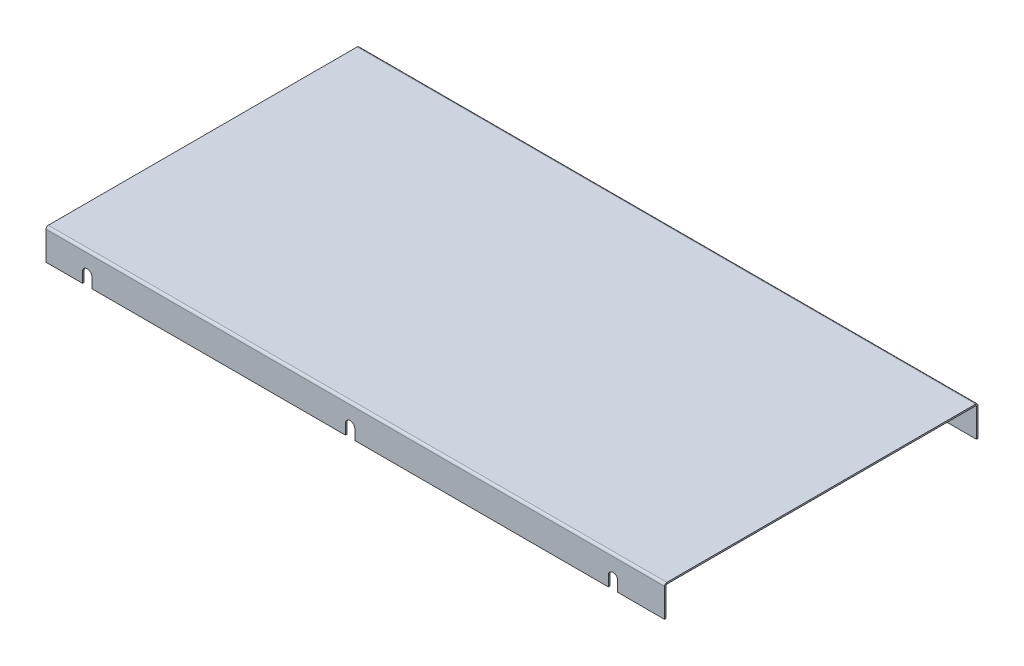
SolidWorks part; units mm, degrees
note: The reader was unsure of these and kept them because the rebuilt part matched: flange length of "边线-法兰1".
material "AISI 304"
ref_plane "前视基准面" through (0, 0, 0) normal (0, 0, 1) x (1, 0, 0)
ref_plane "上视基准面" through (0, 0, 0) normal (0, 1, 0) x (1, 0, 0)
ref_plane "右视基准面" through (0, 0, 0) normal (1, 0, 0) x (0, 0, -1)
other "Configuration Table"
sketch "草图1" plane through (0, 0, 0) normal (0, 1, 0) x (1, 0, 0)
  line L5 (-300, 152) -> (300, 152)
  line L6 (-300, 152) -> (-300, -152)
  line L7 (-300, -152) -> (300, -152)
  line L8 (300, 152) -> (300, -152)
  line L9 (-300, 152) -> (300, -152) construction
  line L10 (-300, -152) -> (300, 152) construction
  point P0 (0, 0)
  dimension "D1" = 600
  dimension "D2" = 304
base flange "基体-法兰1" sketch "草图1" thickness 1.5 reverse thickness direction no parameters "D1"=0.7366
edge flange "边线-法兰1" sketch "草图10" flange profiles "草图10", "草图11" flange angle 90 flange length 30 flange position material inside bend radius 0.7366 thickness 1.5 relief rectangular parameters "D6"=10, "D8"=1
sketch "草图10" plane through (0, -1.5, 152) normal (0, 0, 1) x (-1, 0, 0)
  line L0 (300, 0) -> (-300, 0) construction
  line L1 (300, 0) -> (-300, 0)
  line L2 (-300, 0) -> (-300, 28.5)
  line L3 (-300, 28.5) -> (300, 28.5)
  line L4 (300, 28.5) -> (300, 0)
sketch "草图11" plane through (0, -1.5, -152) normal (0, 0, -1) x (1, 0, 0)
  line L0 (300, 0) -> (-300, 0) construction
  line L1 (300, 0) -> (-300, 0)
  line L2 (-300, 0) -> (-300, 28.5)
  line L3 (-300, 28.5) -> (300, 28.5)
  line L4 (300, 28.5) -> (300, 0)
bend "边线折弯1" bend radius 0.7366 bend angle 90 parameters "D5"=1
bend "边线折弯2" bend radius 0.7366 bend angle 90 parameters "D5"=2
sketch "草图12" plane through (0, 0, -152) normal (0, 0, -1) x (-1, 0, 0)
  line L0 (-250, -30) -> (-250, -20) construction
  line L1 (-300, -30) -> (300, -30) construction
  line L2 (-254.5, -30) -> (-254.5, -20)
  line L3 (-245.5, -30) -> (-245.5, -20)
  line L4 (-300, 0) -> (300, 0) construction
  line L5 (-300, -2.2366) -> (-300, -30) construction
  arc A0 (-254.5, -30) -> (-245.5, -30) centre (-250, -30) ccw
  arc A1 (-245.5, -20) -> (-254.5, -20) centre (-250, -20) ccw
  point P4 (-250, -25)
  dimension "D1" = 20
  dimension "D2" = 9
  dimension "D3" = 50
extrude "切除-拉伸1" cut sketch "草图12" against normal through all normal cut yes
pattern_linear "阵列(线性)1" count 3 spacing 255 along (-1, 0, 0) of "切除-拉伸1"
sketch "折弯-线1" [suppressed] plane through (0, 0, 0) normal (0, 1, 0) x (1, 0, 0)
sketch "边界框1" [suppressed] plane through (0, 0, 0) normal (0, 1, 0) x (1, 0, 0)
sheet metal parameters "钣金6" thickness 1.5 parameters "D1"=0.7366
flat pattern "平板型式6" [suppressed]
sketch "折弯-线2" plane through (0, 0, 0) normal (0, 1, 0) x (1, 0, 0)
sketch3d "边界框2" [suppressed]
  line L0 (300, -152, 0) -> (-300, -152, 0) construction
  line L1 (300, 152, 0) -> (-300, 152, 0) construction
  line L2 (300, -152, 0) -> (300, 152, 0) construction
  line L3 (-300, -152, 0) -> (-300, 152, 0) construction
sheet metal parameters "钣金7" thickness 1.5 parameters "D1"=0.7366
flat pattern "平板型式6" [suppressed]
sketch "折弯-线2" plane through (0, 0, 0) normal (0, 1, 0) x (1, 0, 0)
sketch3d "边界框2" [suppressed]
  line L0 (300, -152, 0) -> (-300, -152, 0) construction
  line L1 (300, 152, 0) -> (-300, 152, 0) construction
  line L2 (300, -152, 0) -> (300, 152, 0) construction
  line L3 (-300, -152, 0) -> (-300, 152, 0) construction
bend of the flat pattern "展平-<边线折弯1>1"
bend of the flat pattern "展平-<边线折弯2>1"
sheet metal parameters "钣金8" thickness 1.5 parameters "D1"=0.7366
flat pattern "平板型式6" [suppressed]
sketch "折弯-线2" plane through (0, 0, 0) normal (0, 1, 0) x (1, 0, 0)
sketch3d "边界框2" [suppressed]
  line L0 (300, -152, 0) -> (-300, -152, 0) construction
  line L1 (300, 152, 0) -> (-300, 152, 0) construction
  line L2 (300, -152, 0) -> (300, 152, 0) construction
  line L3 (-300, -152, 0) -> (-300, 152, 0) construction
bend of the flat pattern "展平-<边线折弯1>1"
bend of the flat pattern "展平-<边线折弯2>1"
sheet metal parameters "钣金9" thickness 1.5 parameters "D1"=0.7366
flat pattern "平板型式6" [suppressed]
sketch "折弯-线2" plane through (0, 0, 0) normal (0, 1, 0) x (1, 0, 0)
sketch3d "边界框2" [suppressed]
  line L0 (300, -152, 0) -> (-300, -152, 0) construction
  line L1 (300, 152, 0) -> (-300, 152, 0) construction
  line L2 (300, -152, 0) -> (300, 152, 0) construction
  line L3 (-300, -152, 0) -> (-300, 152, 0) construction
bend of the flat pattern "展平-<边线折弯1>1"
bend of the flat pattern "展平-<边线折弯2>1"
equation "\"长\"= 1000mm"
equation "\"宽\"= 300mm"
equation "\"高\"= 500mm"
equation "\"D1@草图1\"=\"长\"-400"
equation "\"D2@草图1\"=\"宽\"+4"
